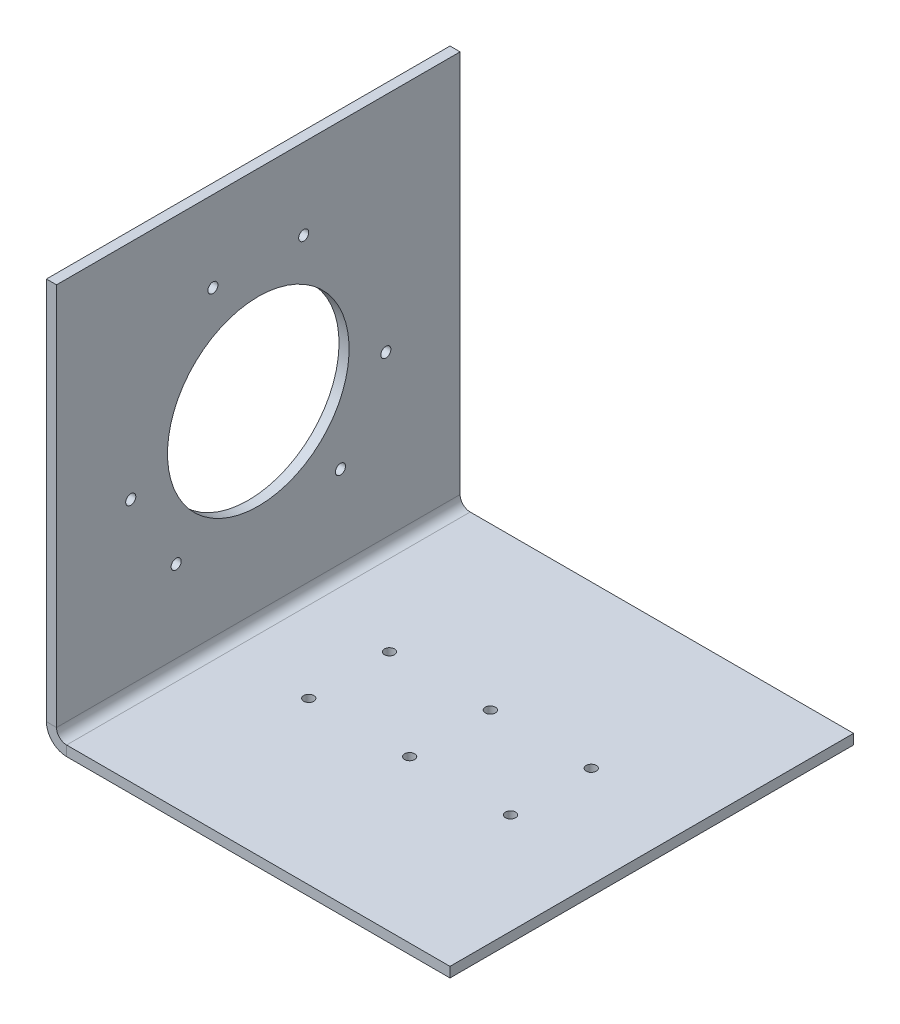
SolidWorks part; units mm, degrees
note: The reader was unsure of these and kept them because the rebuilt part matched: thickness of "Base-Flange1", "Edge-Flange1", "Sheet-Metal1", "Sheet-Metal2", "Sheet-Metal3", "Sheet-Metal4"; flange length of "Edge-Flange1".
ref_plane "Front Plane" through (0, 0, 0) normal (0, 0, 1) x (1, 0, 0)
ref_plane "Top Plane" through (0, 0, 0) normal (0, 1, 0) x (1, 0, 0)
ref_plane "Right Plane" through (0, 0, 0) normal (1, 0, 0) x (0, 0, -1)
sketch "Sketch2" plane through (0, 0, 0) normal (0, 1, 0) x (1, 0, 0)
  line L1 (0, 0) -> (254, 0)
  line L2 (0, 0) -> (0, 254)
  line L3 (0, 254) -> (254, 254)
  line L4 (254, 0) -> (254, 254)
  line L5 (0, 0) -> (254, 254) construction
  line L6 (0, 254) -> (254, 0) construction
  circle A0 centre (190.5, 152.4) radius 3.175
  circle A1 centre (127, 152.4) radius 3.175
  circle A2 centre (63.5, 152.4) radius 3.175
  circle A3 centre (127, 101.6) radius 3.175
  circle A4 centre (63.5, 101.6) radius 3.175
  circle A5 centre (190.5, 101.6) radius 3.175
  point P4 (127, 127)
  dimension "D2" = 6.35
  dimension "D8" = 50.8
  dimension "D1" = 254
  dimension "D3" = 63.5
  dimension "D4" = 101.6
  dimension "D7" = 63.5
  dimension "D9" = 63.5
  dimension "D5" = 3
  dimension "D6" = 2
base flange "Base-Flange1" sketch "Sketch2" thickness 6.35 reverse thickness direction no parameters "D1"=6.35
edge flange "Edge-Flange1" sketch "Sketch9" flange angle 90 flange length 254 flange position material inside bend radius 6.35 thickness 6.35 relief rectangular parameters "D1"=0.7366, "D6"=10
sketch "Sketch9" plane through (0, 0, 0) normal (-1, 0, 0) x (0, 0, 1)
  line L0 (-254, 0) -> (0, 0) construction
  line L1 (-254, 0) -> (0, 0)
  line L2 (-254, 0) -> (-254, 247.65)
  line L3 (-254, 247.65) -> (0, 247.65)
  line L4 (0, 247.65) -> (0, 0)
bend "EdgeBend1" bend radius 6.35 bend angle 90 parameters "D5"=1
sketch "Sketch10" plane through (0, 0, 0) normal (-1, 0, 0) x (0, 0, 1)
  line L0 (-254, -6.35) -> (0, -6.35) construction
  line L1 (0, -6.35) -> (0, 6.35) construction
  line L2 (-254, 6.35) -> (-254, -6.35) construction
  line L3 (0, 6.35) -> (0, 247.65) construction
  line L4 (0, 247.65) -> (-254, 247.65) construction
  line L5 (-254, 247.65) -> (-254, 6.35) construction
  line L6 (-254, -6.35) -> (0, -6.35)
  line L7 (0, -6.35) -> (0, 6.35)
  line L8 (-254, 6.35) -> (-254, -6.35)
  line L9 (0, 6.35) -> (0, 247.65)
  line L10 (0, 247.65) -> (-254, 247.65)
  line L11 (-254, 247.65) -> (-254, 6.35)
  line L12 (-254, 247.65) -> (0, -6.35) construction
  circle A0 centre (-127, 120.65) radius 57.15
  dimension "D1" = 114.3
extrude "Cut-Extrude1" cut sketch "Sketch10" against normal through all contours A0 normal cut yes
sketch "Sketch12" plane through (6.35, 0, 0) normal (1, 0, 0) x (0, 0, -1)
  line L0 (127, 120.65) -> (127, 196.85) construction
  line L1 (98.425, 196.85) -> (155.575, 196.85) construction
  line L4 (0, 247.65) -> (0, 6.35)
  line L5 (0, 6.35) -> (254, 6.35)
  line L6 (254, 6.35) -> (254, 247.65)
  line L7 (254, 247.65) -> (0, 247.65)
  line L8 (0, 247.65) -> (0, 6.35)
  line L9 (0, 6.35) -> (254, 6.35)
  line L10 (254, 6.35) -> (254, 247.65)
  line L11 (254, 247.65) -> (0, 247.65)
  circle A0 centre (127, 120.65) radius 57.15 construction
  circle A1 centre (127, 120.65) radius 57.15
  circle A2 centre (98.425, 196.85) radius 3.175
  circle A3 centre (155.575, 196.85) radius 3.175
  circle A4 centre (207.2786, 107.2967) radius 3.175
  circle A5 centre (178.7036, 57.8033) radius 3.175
  circle A6 centre (75.2964, 57.8033) radius 3.175
  circle A7 centre (46.7214, 107.2967) radius 3.175
  point P23 (127, 120.65)
  dimension "D4" = 6.35
  dimension "D5" = 3
  dimension "D2" = 57.15
  dimension "D3" = 76.2
  dimension "D1" = 0
extrude "Cut-Extrude2" cut sketch "Sketch12" against normal through all contours A6 | A7 | A2 | A3 | A5 | A4 normal cut yes
sketch "Bend-Lines1" [suppressed] plane through (0, 0, 0) normal (0, 1, 0) x (1, 0, 0)
sketch "Bounding-Box1" [suppressed] plane through (0, 0, 0) normal (0, 1, 0) x (1, 0, 0)
sheet metal parameters "Sheet-Metal1" thickness 6.35 parameters "D1"=6.35
flat pattern "Flat-Pattern1" [suppressed]
sketch "Bend-Lines2" plane through (0, 0, 0) normal (0, 1, 0) x (1, 0, 0)
sketch3d "Bounding-Box2" [suppressed]
  line L0 (0, 0, 0) -> (0, 254, 0) construction
  line L1 (-254, 0, 0) -> (-254, 254, 0) construction
  line L2 (0, 0, 0) -> (-254, 0, 0) construction
  line L3 (0, 254, 0) -> (-254, 254, 0) construction
sheet metal parameters "Sheet-Metal2" thickness 6.35 parameters "D1"=6.35, "D7"=3
flat pattern "Flat-Pattern1" [suppressed]
sketch "Bend-Lines2" plane through (0, 0, 0) normal (0, 1, 0) x (1, 0, 0)
  line L0 (1.98, 254) -> (1.98, 0) construction
  line L1 (1.98, 254) -> (1.98, 0) construction
sketch3d "Bounding-Box2" [suppressed]
  line L0 (254, 254, 0) -> (-250.04, 254, 0) construction
  line L1 (254, 0, 0) -> (-250.04, 0, 0) construction
  line L2 (254, 254, 0) -> (254, 0, 0) construction
  line L3 (-250.04, 254, 0) -> (-250.04, 0, 0) construction
bend of the flat pattern "Flatten-<EdgeBend1>1"
sketch "Sketch10-1" [suppressed] plane through (0.96, -3, 0) normal (0, -1, 0) x (0, 0, 1)
  line L6 (-254, -3) -> (0, -3)
  line L7 (0, -3) -> (0, 0.7366)
  line L8 (-254, 0.7366) -> (-254, -3)
  line L9 (0, 0.7366) -> (0, 251)
  line L10 (0, 251) -> (-254, 251)
  line L11 (-254, 251) -> (-254, 0.7366)
sheet metal parameters "Sheet-Metal3" thickness 6.35 parameters "D1"=6.35, "D7"=3
flat pattern "Flat-Pattern1" [suppressed]
sketch "Bend-Lines2" plane through (0, 0, 0) normal (0, 1, 0) x (1, 0, 0)
  line L0 (5.2191, 254) -> (5.2191, 0) construction
  line L1 (5.2191, 254) -> (5.2191, 0) construction
sketch3d "Bounding-Box2" [suppressed]
  line L0 (254, 254, 0) -> (-243.5618, 254, 0) construction
  line L1 (254, 0, 0) -> (-243.5618, 0, 0) construction
  line L2 (254, 254, 0) -> (254, 0, 0) construction
  line L3 (-243.5618, 254, 0) -> (-243.5618, 0, 0) construction
bend of the flat pattern "Flatten-<EdgeBend1>1"
sketch "Sketch10-1" plane through (4.0882, -6.35, 0) normal (0, -1, 0) x (0, 0, 1)
  line L6 (-254, -6.35) -> (0, -6.35)
  line L7 (0, -6.35) -> (0, 6.35)
  line L8 (-254, 6.35) -> (-254, -6.35)
  line L9 (0, 6.35) -> (0, 247.65)
  line L10 (0, 247.65) -> (-254, 247.65)
  line L11 (-254, 247.65) -> (-254, 6.35)
  line L12 (-254, 247.65) -> (0, -6.35) construction
  circle A0 centre (-127, 120.65) radius 57.15
  dimension "D1" = 114.3
sheet metal parameters "Sheet-Metal4" thickness 6.35 parameters "D1"=6.35, "D7"=3
flat pattern "Flat-Pattern1" [suppressed]
sketch "Bend-Lines2" plane through (0, 0, 0) normal (0, 1, 0) x (1, 0, 0)
  line L0 (5.2191, 254) -> (5.2191, 0) construction
  line L1 (5.2191, 254) -> (5.2191, 0) construction
sketch3d "Bounding-Box2" [suppressed]
  line L0 (254, 254, 0) -> (-243.5618, 254, 0) construction
  line L1 (254, 0, 0) -> (-243.5618, 0, 0) construction
  line L2 (254, 254, 0) -> (254, 0, 0) construction
  line L3 (-243.5618, 254, 0) -> (-243.5618, 0, 0) construction
bend of the flat pattern "Flatten-<EdgeBend1>1"
sketch "Sketch10-1" plane through (4.0882, -6.35, 0) normal (0, -1, 0) x (0, 0, 1)
  line L6 (-254, -6.35) -> (0, -6.35)
  line L7 (0, -6.35) -> (0, 6.35)
  line L8 (-254, 6.35) -> (-254, -6.35)
  line L9 (0, 6.35) -> (0, 247.65)
  line L10 (0, 247.65) -> (-254, 247.65)
  line L11 (-254, 247.65) -> (-254, 6.35)
  line L12 (-254, 247.65) -> (0, -6.35) construction
  circle A0 centre (-127, 120.65) radius 57.15
  dimension "D1" = 114.3
